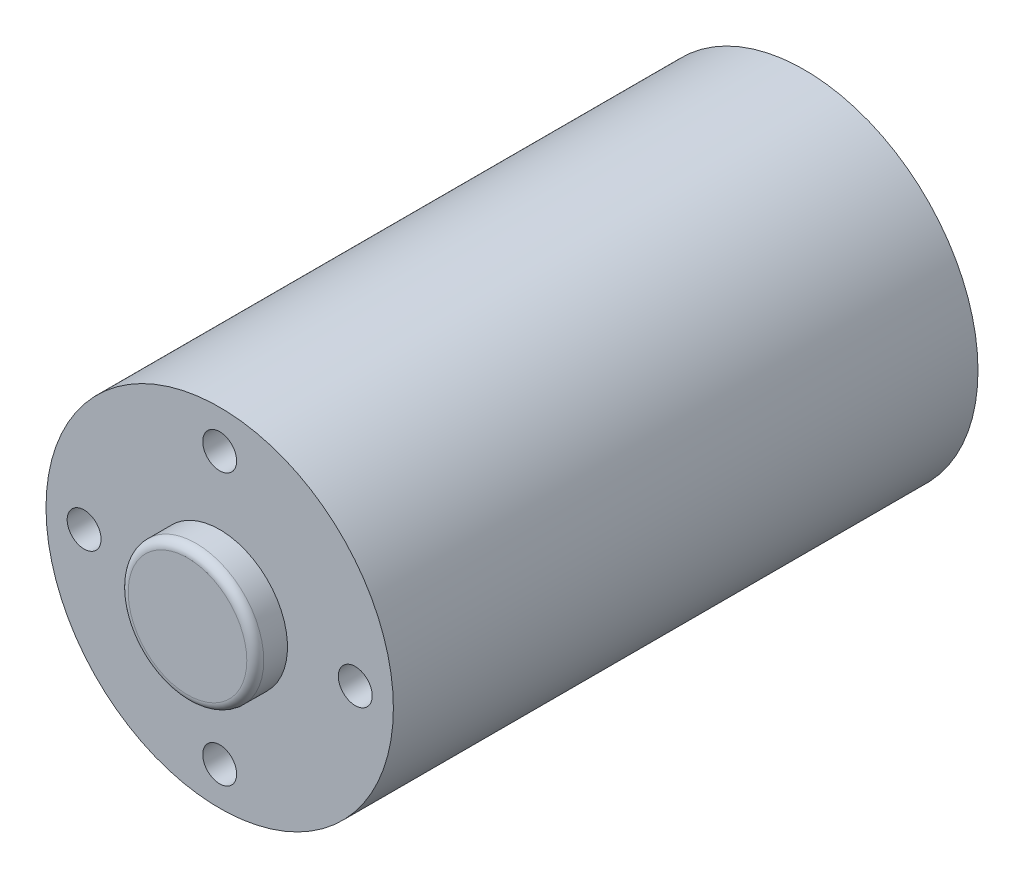
SolidWorks part; units mm, degrees
ref_plane "Front Plane" through (0, 0, 0) normal (0, 0, 1) x (1, 0, 0)
ref_plane "Top Plane" through (0, 0, 0) normal (0, 1, 0) x (1, 0, 0)
ref_plane "Right Plane" through (0, 0, 0) normal (1, 0, 0) x (0, 0, -1)
sketch "Sketch1" plane through (0, 0, 0) normal (0, 0, 1) x (1, 0, 0)
  circle A0 centre (0, 0) radius 10.25
  dimension "D1" = 20.5
extrude "Boss-Extrude1" add sketch "Sketch1" along normal blind 19 and the other way blind 19
sketch "Sketch2" plane through (0, 0, 19) normal (0, 0, 1) x (1, 0, 0)
  circle A0 centre (0, 0) radius 4
extrude "Boss-Extrude2" add sketch "Sketch2" along normal blind 1.9
sketch "Sketch3" plane through (0, 0, -19) normal (0, 0, -1) x (-1, 0, 0)
  circle A0 centre (0, 0) radius 4
  dimension "D1" = 8
extrude "Boss-Extrude3" add sketch "Sketch3" along normal blind 1
sketch "Sketch4" plane through (0, 0, 19) normal (0, 0, 1) x (1, 0, 0)
  circle A0 centre (0, 0) radius 8
  circle A1 centre (0, 8) radius 1
  circle A2 centre (8, 0) radius 1
  circle A3 centre (0, -8) radius 1
  circle A4 centre (-8, 0) radius 1
  point P14 (0, 0)
  dimension "D1" = 4
extrude "Cut-Extrude1" cut sketch "Sketch4" against normal blind 3.5 contours A0 A1 | A0 A4 | A0 A3 | A0 A2 | A0 A2 | A0 A3 | A0 A4 | A1 region at (7.5645, 0, 19) region at (8.413, 0, 19) region at (0, 7.5645, 19) region at (0, -8.413, 19) region at (0, -7.5645, 19) region at (-7.5645, 0, 19) region at (-8.413, 0, 19)
fillet "Fillet1" radius 0.5 1 edges at (4, 0, 20.9)
ref_plane "Plane1" through (0, 0, 0) normal (0, 0, -1) x (-1, 0, 0)
mirror "Mirror1" about plane through (0, 0, 0) normal (0, 0, -1) of "Cut-Extrude1"
sketch "Sketch7" plane through (0, 0, -19) normal (0, 0, -1) x (-1, 0, 0)
  circle A0 centre (0, 0) radius 10.25
extrude "Cut-Extrude3" cut sketch "Sketch7" against normal blind 3.5 and the other way blind 5.5
sketch "Sketch9" plane through (0, 0, -15.5) normal (0, 0, -1) x (-1, 0, 0)
  circle A0 centre (0, 0) radius 1.5
  dimension "D1" = 3
extrude "Cut-Extrude5" cut sketch "Sketch9" against normal blind 5
